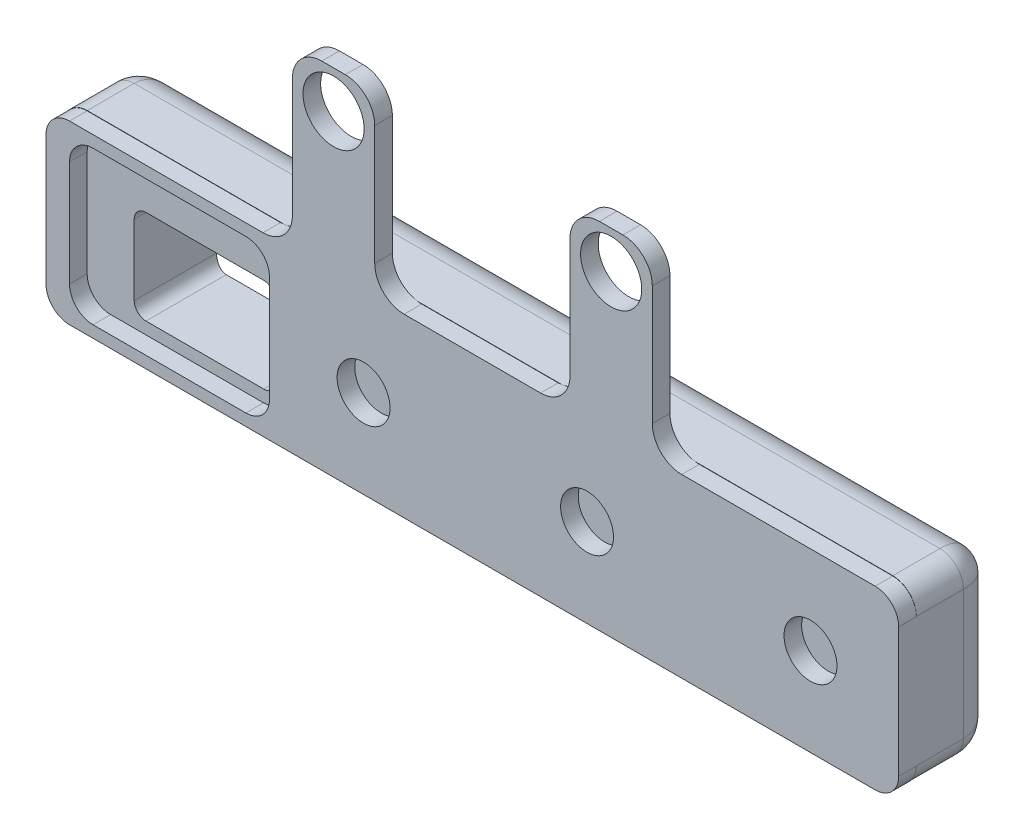
SolidWorks part; units mm, degrees
ref_plane "Front Plane" through (0, 0, 0) normal (0, 0, 1) x (1, 0, 0)
ref_plane "Top Plane" through (0, 0, 0) normal (0, 1, 0) x (1, 0, 0)
ref_plane "Right Plane" through (0, 0, 0) normal (1, 0, 0) x (0, 0, -1)
sketch "Sketch1" plane through (0, 0, 0) normal (0, 0, 1) x (1, 0, 0)
  line L0 (10.0074, 11.5687) -> (10.0074, -3.4313) construction
  line L1 (-24.2426, 11.5687) -> (-7.7926, 11.5687)
  line L2 (-26.2426, 9.5687) -> (-26.2426, -1.4313)
  line L3 (-24.2426, -3.4313) -> (44.2574, -3.4313)
  line L4 (46.2574, 9.5687) -> (46.2574, -1.4313)
  line L5 (-5.2926, 14.0687) -> (-5.2926, 24.2087)
  line L6 (-22.2426, 10.5687) -> (-9.2426, 10.5687)
  line L7 (-24.2426, 8.5687) -> (-24.2426, -0.4313)
  line L8 (-22.2426, -2.4313) -> (-9.2426, -2.4313)
  line L9 (-7.2426, 8.5687) -> (-7.2426, -0.4313)
  line L10 (-2.7926, 26.7087) -> (-0.7926, 26.7087)
  line L11 (1.7074, 24.2087) -> (1.7074, 14.0687)
  line L12 (18.3074, 14.0687) -> (18.3074, 24.2087)
  line L13 (20.8074, 26.7087) -> (22.8074, 26.7087)
  line L14 (25.3074, 24.2087) -> (25.3074, 14.0687)
  line L15 (4.2074, 11.5687) -> (15.8074, 11.5687)
  line L16 (27.8074, 11.5687) -> (44.2574, 11.5687)
  circle A0 centre (38.7574, 4.0687) radius 2.25
  circle A1 centre (19.7574, 4.0687) radius 2.25
  circle A2 centre (0.7574, 4.0687) radius 2.25
  arc A3 (-24.2426, -0.4313) -> (-22.2426, -2.4313) centre (-22.2426, -0.4313) ccw
  arc A4 (-9.2426, -2.4313) -> (-7.2426, -0.4313) centre (-9.2426, -0.4313) ccw
  arc A5 (-9.2426, 10.5687) -> (-7.2426, 8.5687) centre (-9.2426, 8.5687) cw
  arc A6 (-22.2426, 10.5687) -> (-24.2426, 8.5687) centre (-22.2426, 8.5687) ccw
  arc A7 (44.2574, -3.4313) -> (46.2574, -1.4313) centre (44.2574, -1.4313) ccw
  arc A8 (44.2574, 11.5687) -> (46.2574, 9.5687) centre (44.2574, 9.5687) cw
  arc A9 (-26.2426, -1.4313) -> (-24.2426, -3.4313) centre (-24.2426, -1.4313) ccw
  arc A10 (-24.2426, 11.5687) -> (-26.2426, 9.5687) centre (-24.2426, 9.5687) ccw
  circle A11 centre (-1.7926, 23.5087) radius 2.6
  arc A12 (-0.7926, 26.7087) -> (1.7074, 24.2087) centre (-0.7926, 24.2087) cw
  arc A13 (-5.2926, 24.2087) -> (-2.7926, 26.7087) centre (-2.7926, 24.2087) cw
  circle A14 centre (21.8074, 23.5087) radius 2.6
  arc A15 (22.8074, 26.7087) -> (25.3074, 24.2087) centre (22.8074, 24.2087) cw
  arc A16 (18.3074, 24.2087) -> (20.8074, 26.7087) centre (20.8074, 24.2087) cw
  arc A17 (25.3074, 14.0687) -> (27.8074, 11.5687) centre (27.8074, 14.0687) ccw
  arc A18 (18.3074, 14.0687) -> (15.8074, 11.5687) centre (15.8074, 14.0687) cw
  arc A19 (1.7074, 14.0687) -> (4.2074, 11.5687) centre (4.2074, 14.0687) ccw
  arc A20 (-5.2926, 14.0687) -> (-7.7926, 11.5687) centre (-7.7926, 14.0687) cw
  point P16 (-26.2426, 4.0687)
  point P29 (46.2574, 11.5687)
  point P32 (-26.2426, -3.4313)
  point P35 (-26.2426, 11.5687)
  point P44 (1.7074, 26.7087)
  point P47 (-5.2926, 26.7087)
  point P58 (0, 0)
  point P59 (0, 0)
  point P62 (25.3074, 11.5687)
  point P65 (18.3074, 11.5687)
  point P68 (1.7074, 11.5687)
  dimension "D3" = 4.5
  dimension "D6" = 4.5
  dimension "D8" = 19
  dimension "D9" = 4.5
  dimension "D15" = 2
  dimension "D16" = 2
  dimension "D17" = 5.2
  dimension "D21" = 2.5
  dimension "D23" = 5.2
  dimension "D28" = 2.5
  dimension "D1" = 72.5
  dimension "D2" = 15
  dimension "D4" = 7.5
  dimension "D5" = 7.5
  dimension "D7" = 19
  dimension "D10" = 9.25
  dimension "D11" = 1
  dimension "D12" = 1
  dimension "D13" = 2
  dimension "D14" = 19
  dimension "D18" = 7
  dimension "D19" = 3.2
  dimension "D20" = 3.5
  dimension "D22" = 3.2
  dimension "D24" = 3.5
  dimension "D25" = 7
  dimension "D26" = 23.6
  dimension "D27" = 11.8
extrude "Boss-Extrude1" add sketch "Sketch1" along normal blind 1.5
sketch "Sketch2" plane through (0, 0, 0) normal (0, 0, -1) x (-1, 0, 0)
  line L1 (-44.2574, 11.592) -> (24.2426, 11.592)
  line L2 (-46.2574, 9.592) -> (-46.2574, -1.408)
  line L3 (-44.2574, -3.408) -> (24.2426, -3.408)
  line L4 (26.2426, 9.592) -> (26.2426, -1.408)
  line L5 (9.2426, 6.592) -> (19.2426, 6.592)
  line L6 (8.2426, 5.592) -> (8.2426, -0.408)
  line L7 (9.2426, -1.408) -> (19.2426, -1.408)
  line L8 (20.2426, 5.592) -> (20.2426, -0.408)
  arc A0 (24.2426, 11.592) -> (26.2426, 9.592) centre (24.2426, 9.592) cw
  arc A1 (24.2426, -3.408) -> (26.2426, -1.408) centre (24.2426, -1.408) ccw
  arc A2 (-46.2574, -1.408) -> (-44.2574, -3.408) centre (-44.2574, -1.408) ccw
  arc A3 (-44.2574, 11.592) -> (-46.2574, 9.592) centre (-44.2574, 9.592) ccw
  arc A4 (8.2426, -0.408) -> (9.2426, -1.408) centre (9.2426, -0.408) ccw
  arc A5 (19.2426, -1.408) -> (20.2426, -0.408) centre (19.2426, -0.408) ccw
  arc A6 (19.2426, 6.592) -> (20.2426, 5.592) centre (19.2426, 5.592) cw
  arc A7 (9.2426, 6.592) -> (8.2426, 5.592) centre (9.2426, 5.592) ccw
  point P20 (20.2426, -1.408)
  point P23 (20.2426, 6.592)
  dimension "D2" = 2
  dimension "D7" = 1
  dimension "D1" = 72.5
  dimension "D3" = 15
  dimension "D4" = 12
  dimension "D5" = 8
  dimension "D6" = 18
extrude "Boss-Extrude2" add sketch "Sketch2" along normal blind 7
fillet "Fillet1" radius 3 8 edges at (45.6716, 11.0062, -7) (45.6716, -2.8222, -7) (46.2574, 4.092, -7) (10.0074, -3.408, -7) (-25.6568, -2.8222, -7) (-26.2426, 4.092, -7) (-25.6568, 11.0062, -7) (10.0074, 11.592, -7)
